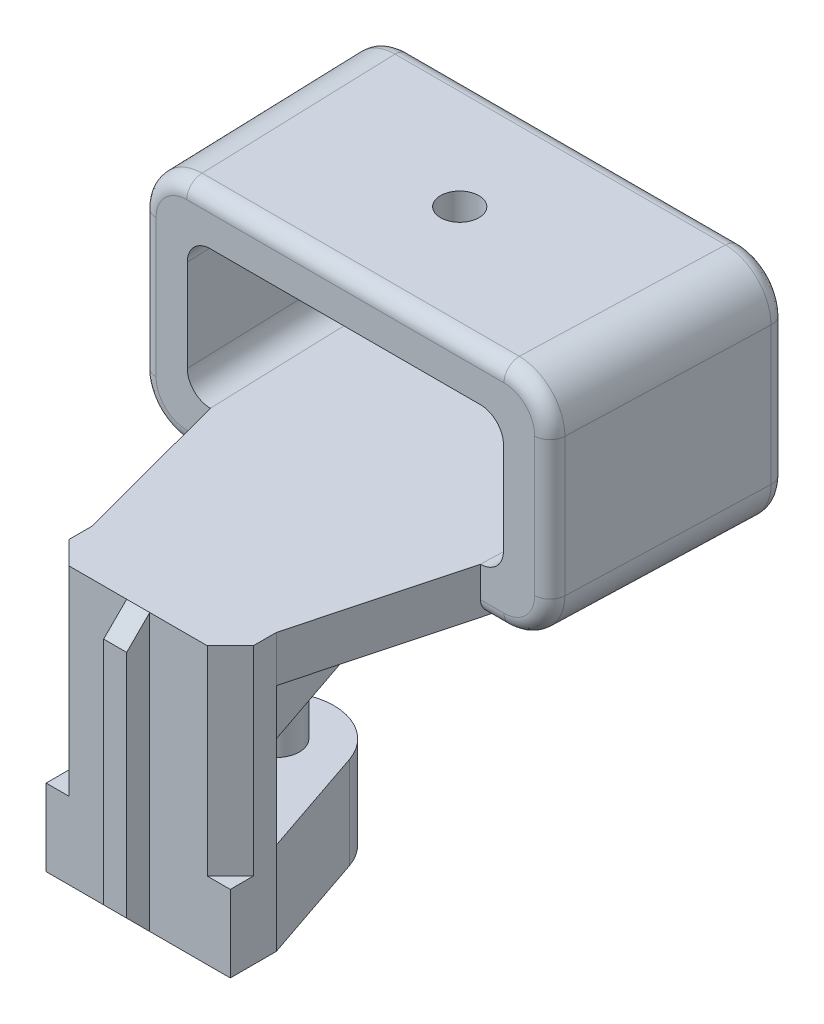
SolidWorks part; units mm, degrees
ref_plane "정면" through (0, 0, 0) normal (0, 0, 1) x (1, 0, 0)
ref_plane "윗면" through (0, 0, 0) normal (0, 1, 0) x (1, 0, 0)
ref_plane "우측면" through (0, 0, 0) normal (1, 0, 0) x (0, 0, -1)
sketch "스케치1" plane through (0, 0, 0) normal (0, 1, 0) x (1, 0, 0)
  line L0 (-12, -12) -> (12, -12)
  line L1 (12, -12) -> (7.101, 2.4135)
  line L2 (-12, -12) -> (-7.101, 2.4135)
  circle A0 centre (0, 0) radius 3
  arc A1 (7.101, 2.4135) -> (-7.101, 2.4135) centre (0, 0) ccw
  point P9 (0, -12)
  dimension "D1" = 6
  dimension "D2" = 15
  dimension "D3" = 24
  dimension "D4" = 12
extrude "보스-돌출1" add sketch "스케치1" along normal blind 12
sketch "스케치2" plane through (0, 0, 0) normal (0, 1, 0) x (1, 0, 0)
  line L0 (-12, -12) -> (12, -12)
  line L1 (12, -12) -> (12, -18)
  line L2 (12, -18) -> (-12, -18)
  line L3 (-12, -18) -> (-12, -12)
  dimension "D1" = 6
extrude "보스-돌출2" add sketch "스케치2" along normal blind 36
sketch "스케치3" plane through (0, 36, 0) normal (0, 1, 0) x (1, 0, 0)
  line L3 (-7.101, 2.4135) -> (-12, -12)
  line L4 (-12, -12) -> (12, -12)
  line L5 (12, -12) -> (7.101, 2.4135)
  line L6 (-7.101, 2.4135) -> (-12, -12)
  line L7 (-12, -12) -> (12, -12)
  line L8 (12, -12) -> (7.101, 2.4135)
  circle A0 centre (0, 0) radius 3 construction
  arc A1 (7.101, 2.4135) -> (-7.101, 2.4135) centre (0, 0) ccw
  arc A2 (7.101, 2.4135) -> (-7.101, 2.4135) centre (0, 0) ccw
  circle A3 centre (0, 0) radius 3
  dimension "D1" = 0
extrude "보스-돌출3" add sketch "스케치3" against normal blind 12
sketch "스케치5" plane through (0, 36, 0) normal (0, 1, 0) x (1, 0, 0)
  line L0 (-20.6, 9) -> (20.6, 9) construction
  line L1 (20.6, 9) -> (21.6, 39)
  line L2 (21.6, 39) -> (-21.6, 39)
  line L3 (-21.6, 39) -> (-20.6, 9)
  line L4 (-20.6, 9) -> (-12, -12)
  line L5 (-12, -12) -> (12, -12)
  line L6 (12, -12) -> (20.6, 9)
  circle A0 centre (0, 0) radius 3 construction
  circle A1 centre (0, 0) radius 3
  point P2 (0, 9)
  point P5 (0, 39)
  dimension "D1" = 41.2
  dimension "D2" = 43.2
  dimension "D3" = 30
  dimension "D4" = 9
extrude "보스-돌출5" add sketch "스케치5" against normal blind 6
sketch "스케치8" plane through (0, 30, 0) normal (0, -1, 0) x (1, 0, 0)
  line L0 (-27.6033, -39) -> (-21.6, -39)
  line L1 (-20.6, -9) -> (-26.6033, -9)
  line L2 (20.6, -9) -> (26.6033, -9)
  line L5 (26.5967, -8.8001) -> (27.5967, -38.8001)
  line L6 (26.6033, -9) -> (27.6033, -39)
  line L7 (-20.6, -9) -> (-21.6, -39)
  line L8 (-27.5967, -38.8001) -> (-26.5967, -8.8001)
  line L9 (-27.6033, -39) -> (-26.6033, -9)
  line L10 (21.6, -39) -> (20.6, -9)
  line L11 (21.6, -39) -> (27.6033, -39)
  dimension "D1" = 6
  dimension "D2" = 6
extrude "보스-돌출7" add sketch "스케치8" against normal blind 30
sketch "스케치9" plane through (0, 0, 0) normal (1, 0, 0) x (0, 0, -1)
  line L0 (33.7, 30) -> (6.7, 25)
  line L1 (39, 30) -> (9, 30) construction
  line L2 (6.7, 25) -> (6.7, 30)
  line L3 (2.4135, 30) -> (7.5, 30) construction
  line L4 (6.7, 30) -> (33.7, 30)
  dimension "D1" = 27
  dimension "D2" = 5
  dimension "D3" = 6.7
extrude "보스-돌출8" add sketch "스케치9" along normal mid plane 6
sketch "스케치10" plane through (0, 60, 0) normal (0, 1, 0) x (1, 0, 0)
  line L0 (20.6, 9) -> (21.6, 39) construction
  line L2 (20.6, 9) -> (21.6, 39)
  line L4 (-21.7, 39) -> (21.6, 39)
  line L6 (-20.6, 9) -> (20.6, 9)
  line L7 (-21.7, 39) -> (-20.6, 9)
  circle A0 centre (-0.1013, 24) radius 2.5
  dimension "D1" = 5
  dimension "D2" = 15
extrude "보스-돌출9" add sketch "스케치10" against normal blind 6
fillet "필렛1" radius 3 4 edges at (-21.1, 54, -24) (-21.1, 36, -24) (21.1, 36, -24) (21.1, 54, -24)
fillet "필렛2" radius 6 4 edges at (-27.1033, 60, -24) (-27.1033, 30, -24) (27.1033, 30, -24) (27.1033, 60, -24)
sketch "스케치11" plane through (0, 0, 0) normal (1, 0, 0) x (0, 0, -1)
  line L0 (-12, 24) -> (-12, 12)
  line L1 (-12, 12) -> (-9, 12)
  line L2 (-9, 12) -> (-9, 24)
  line L3 (-12, 24) -> (2.4135, 24) construction
  line L4 (-9, 24) -> (-12, 24)
  line L5 (-18, 36) -> (-18, 0)
  line L6 (-18, 0) -> (-21, 3)
  line L7 (-21, 3) -> (-21, 33)
  line L8 (-21, 33) -> (-18, 36)
  dimension "D1" = 3
  dimension "D2" = 3
  dimension "D3" = 3
  dimension "D4" = 3
extrude "보스-돌출10" add sketch "스케치11" along normal mid plane 3
sketch "스케치12" plane through (0, 0, -9) normal (0, 0, 1) x (1, 0, 0)
  line L0 (-38.0438, 36) -> (35.8108, 36)
  line L1 (35.8108, 36) -> (35.8108, 40.7102)
  line L2 (35.8108, 40.7102) -> (-38.0438, 40.7102)
  line L3 (-38.0438, 40.7102) -> (-38.0438, 36)
extrude "컷-돌출1" cut sketch "스케치12" along normal blind 13
sketch "스케치13" plane through (0, 36, 0) normal (0, 1, 0) x (1, 0, 0)
  line L0 (-17.5983, 9) -> (-12, -12)
  line L1 (17.5983, 9) -> (12, -12)
  line L2 (-17.5983, 9) -> (-22.9421, 9)
  line L3 (-26.6033, 9) -> (-20.6, 9) construction
  line L4 (-22.9421, 9) -> (-14.2209, -12)
  line L5 (-14.2209, -12) -> (-12, -12)
  line L6 (12, -12) -> (13.7495, -12)
  line L7 (13.7495, -12) -> (23.6017, 9)
  line L8 (20.6, 9) -> (26.6033, 9) construction
  line L9 (23.6017, 9) -> (17.5983, 9)
extrude "컷-돌출2" cut sketch "스케치13" against normal blind 13
fillet "필렛3" radius 2 17 edges at (19.0992, 30, -9) (24.845, 31.7574, -9) (26.6033, 45, -9) (24.845, 58.2426, -9) (-19.0992, 30, -9) (-24.845, 31.7574, -9) (-26.6033, 45, -9) (-24.845, 58.2426, -9) (-25.845, 58.2426, -39) (-27.6033, 45, -39) (-25.845, 31.7574, -39) (0, 30, -39) (25.845, 31.7574, -39) (27.6033, 45, -39) (25.845, 58.2426, -39) (0, 60, -9) (0, 60, -39)
chamfer "모따기1" distance 3 angle 45 2 edges at (12, 18, 18) (-12, 18, 18)
extrude "보스-돌출11" add sketch "스케치2<2>" along normal blind 10
sketch "스케치2<2>" plane through (0, 0, 0) normal (0, 1, 0) x (1, 0, 0) same geometry as "스케치2"
extrude "보스-돌출12" add sketch "스케치3<2>" against normal blind 36 contours A3 region at (0, 36, 0)
sketch "스케치3<2>" plane through (0, 36, 0) normal (0, 1, 0) x (1, 0, 0) same geometry as "스케치3"
